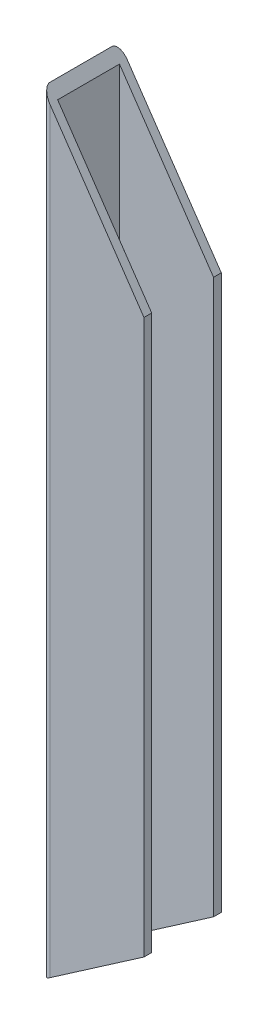
SolidWorks part; units mm, degrees
ref_plane "Спереди" through (0, 0, 0) normal (0, 0, 1) x (1, 0, 0)
ref_plane "Сверху" through (0, 0, 0) normal (0, 1, 0) x (1, 0, 0)
ref_plane "Справа" through (0, 0, 0) normal (1, 0, 0) x (0, 0, -1)
sketch "Эскиз1" plane through (0, 0, 0) normal (0, 1, 0) x (1, 0, 0)
  line L1 (-37, 15) -> (37, 15)
  line L2 (-40, 12) -> (-40, -12)
  line L3 (-37, -15) -> (37, -15)
  line L4 (40, 12) -> (40, -12)
  line L5 (-40, 15) -> (40, -15) construction
  line L6 (-40, -15) -> (40, 15) construction
  arc A0 (-37, 15) -> (-40, 12) centre (-37, 12) ccw
  arc A1 (-40, -12) -> (-37, -15) centre (-37, -12) ccw
  arc A2 (37, -15) -> (40, -12) centre (37, -12) ccw
  arc A3 (37, 15) -> (40, 12) centre (37, 12) cw
  point P0 (0, 0)
  dimension "D1" = 3
extrude "Вытянуть-Тонкостенный1" add sketch "Эскиз1" along normal blind 300 thin thin type one direction reverse wall 3
sketch "Эскиз2" plane through (0, 300, 0) normal (0, 1, 0) x (1, 0, 0)
  line L1 (-0.5, -21.5541) -> (41.1465, -21.5541)
  line L2 (-0.5, -21.5541) -> (-0.5, 20.9728)
  line L3 (-0.5, 20.9728) -> (41.1465, 20.9728)
  line L4 (41.1465, -21.5541) -> (41.1465, 20.9728)
extrude "Вырез-Вытянуть1" cut sketch "Эскиз2" against normal through all
sketch "Эскиз3" plane through (0, 0, 15) normal (0, 0, 1) x (1, 0, 0)
  line L0 (-40, 300) -> (-0.5, 242.2094)
  line L1 (-0.5, 0) -> (-0.5, 300) construction
  line L2 (-0.5, 242.2094) -> (-0.5, 27.2718)
  line L3 (-0.5, 27.2718) -> (-40, 0)
  line L4 (-40, 0) -> (-40, 300)
extrude "Вырез-Вытянуть2" cut sketch "Эскиз3" against normal through all flip side to cut
